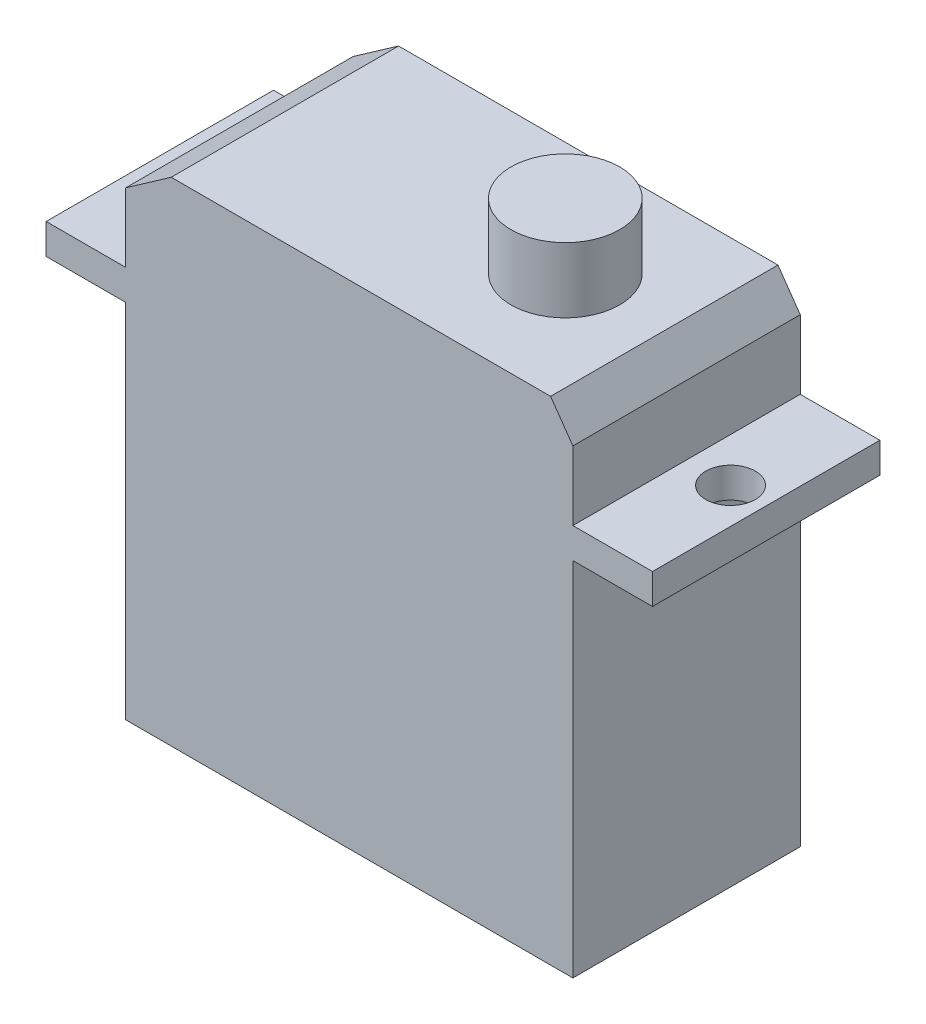
SolidWorks part; units mm, degrees
material "6061-T6 (SS)"
ref_plane "XY" through (0, 0, 0) normal (0, 0, 1) x (1, 0, 0)
ref_plane "XZ" through (0, 0, 0) normal (0, 1, 0) x (1, 0, 0)
ref_plane "YZ" through (0, 0, 0) normal (1, 0, 0) x (0, 0, -1)
ref_axis "X" through (-88.99, 0, 0) along (1, 0, 0)
ref_axis "Y" through (0, -55, 0) along (0, 1, 0)
ref_axis "Z" through (0, 0, 55) along (0, 0, -1)
sketch "Sketch1" plane through (0, 0, 0) normal (0, 0, 1) x (1, 0, 0)
  line L0 (-14.75, 11.925) -> (-20, 11.925)
  line L1 (-14.75, -11.925) -> (14.75, -11.925)
  line L2 (-14.75, -11.925) -> (-14.75, 11.925)
  line L4 (14.75, -11.925) -> (14.75, 11.925)
  line L5 (-14.75, -11.925) -> (14.75, 11.925) construction
  line L6 (-14.75, 11.925) -> (14.75, -11.925) construction
  line L7 (-20, 11.925) -> (-20, 13.925)
  line L8 (-20, 13.925) -> (-14.75, 13.925)
  line L9 (-14.75, 13.925) -> (-14.75, 18.4744)
  line L10 (-14.75, 18.4744) -> (-11.75, 20.575)
  line L11 (-11.75, 20.575) -> (13.2791, 20.575)
  line L12 (13.2791, 20.575) -> (14.75, 18.4744)
  line L13 (14.75, 18.4744) -> (14.75, 13.925)
  line L14 (14.75, 13.925) -> (20, 13.925)
  line L15 (20, 13.925) -> (20, 11.925)
  line L16 (20, 11.925) -> (14.75, 11.925)
  point P0 (0, 0)
  dimension "D1" = 23.85
  dimension "D2" = 29.5
  dimension "D3" = 8.65
  dimension "D4" = 40
  dimension "D5" = 2
  dimension "D6" = 125
  dimension "D7" = 3
extrude "Boss-Extrude1" add sketch "Sketch1" along normal mid plane 15
sketch "Sketch2" plane through (0, 20.575, 0) normal (0, 1, 0) x (1, 0, 0)
  line L0 (0, 0) -> (14.75, 0) construction
  line L1 (14.75, -7.5) -> (14.75, 7.5) construction
  circle A0 centre (6.75, 0) radius 3.5871
  point P3 (7.375, 0)
  point P8 (4.2767, 0)
  dimension "D1" = 8
extrude "Boss-Extrude2" add sketch "Sketch2" along normal blind 4.3
hole_wizard "#4 Clearance Hole1" positions "Sketch3" profile "Sketch4" hole size "#4" standard "ANSI Inch"
sketch "Sketch3" plane through (0, 13.925, 0) normal (0, 1, 0) x (1, 0, 0)
  line L0 (-17.65, 0) -> (17.65, 0) construction
  point P0 (-17.65, 0)
  point P2 (17.65, 0)
  dimension "D1" = 35.3
sketch "Sketch4" plane through (-17.65, 13.925, 0) normal (1, 0, 0) x (0, 0, 1)
  line L0 (0, 0) -> (0, 6.8206)
  line L1 (0, 6.8206) -> (1.6319, 5.84)
  line L2 (1.6319, 5.84) -> (1.6319, 0)
  line L5 (1.6319, 0) -> (0, 0)
  line L10 (0, 6.8206) -> (-1.632, 5.84) construction
  line L11 (0, -6.35) -> (0, 107.95) construction
  dimension "Hole Dia." = 3.2639
  dimension "Hole Depth" = 5.84
  dimension "Drill Angle" = 118
